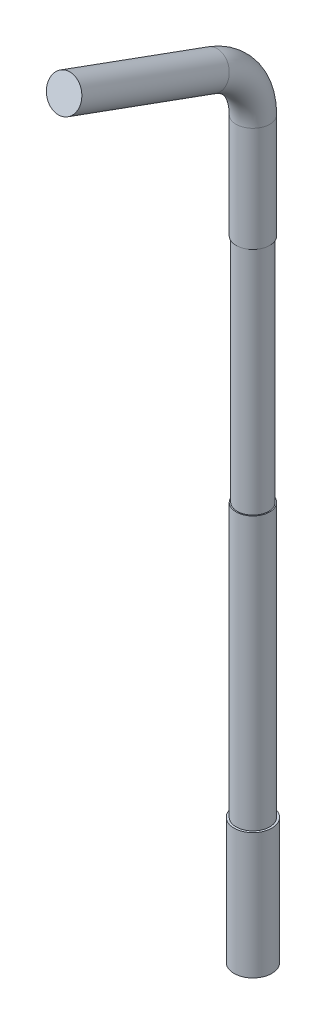
SolidWorks part; units mm, degrees
material "Stainless Steel (ferritic)"
ref_plane "Front Plane" through (0, 0, 0) normal (0, 0, 1) x (1, 0, 0)
ref_plane "Top Plane" through (0, 0, 0) normal (0, 1, 0) x (1, 0, 0)
ref_plane "Right Plane" through (0, 0, 0) normal (1, 0, 0) x (0, 0, -1)
ref_plane "Plane1" through (0, 19, 0) normal (0, 1, 0) x (-1, 0, 0)
sketch "Sketch1" plane through (0, 0, 0) normal (1, 0, 0) x (0, 0, -1)
  line L0 (-7.5, 0) -> (-7.5, 35)
  line L1 (55, 0) -> (-55, 0) construction
  line L2 (-9.4739, 37.8191) -> (-16.5, 40.3764)
  line L3 (0, 55) -> (0, -55) construction
  arc A0 (-7.5, 35) -> (-9.4739, 37.8191) centre (-10.5, 35) ccw
  dimension "D1" = 3
  dimension "D2" = 7.5
  dimension "D3" = 35
  dimension "D4" = 9
  dimension "D5" = 70
sketch "Sketch2" plane through (0, 0, 0) normal (0, 1, 0) x (1, 0, 0)
  circle A0 centre (0, -7.5) radius 0.8
  dimension "D1" = 1.6
sweep "Sweep1" add profiles "Sketch2" path "Sketch1"
sketch "Sketch4" plane through (0, 0, 0) normal (0, 1, 0) x (1, 0, 0)
  circle A0 centre (0, -7.5) radius 0.9
  dimension "D1" = 1.8
extrude "Extrude1" add sketch "Sketch4" along normal blind 6
sketch "Sketch5" plane through (0, 19, 0) normal (0, 1, 0) x (-1, 0, 0)
  circle A0 centre (0, 7.5) radius 0.75
  dimension "D1" = 1.5
extrude "Extrude3" cut sketch "Sketch5" along normal blind 11 flip side to cut
ref_axis "Axis1" through (0, 30, 7.5) along (0, -1, 0)
